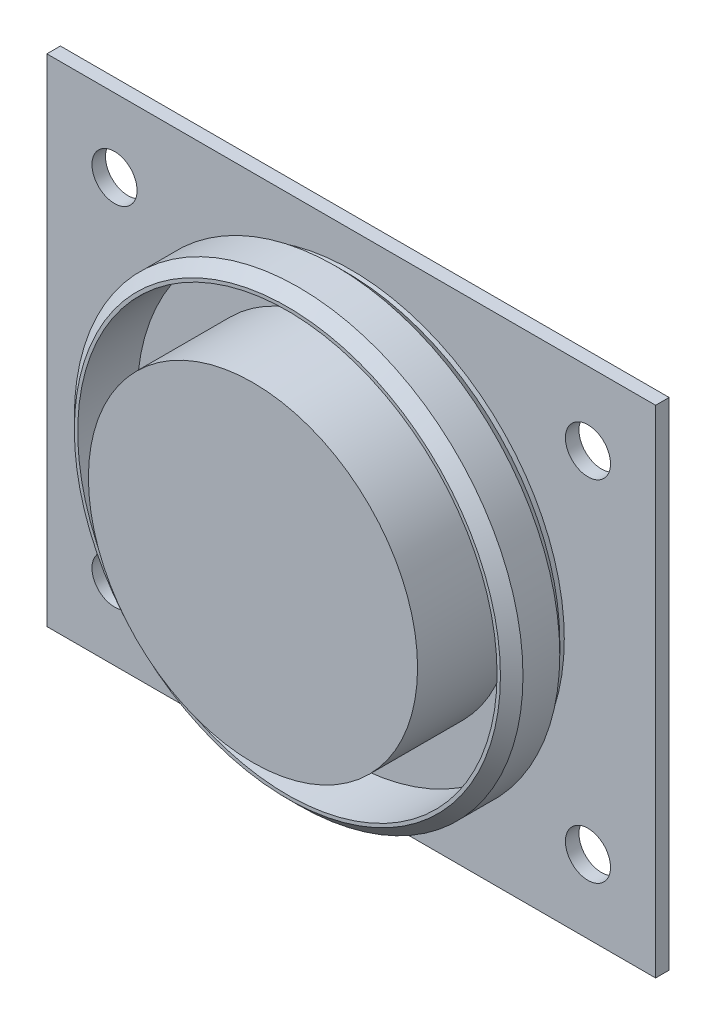
SolidWorks part; units mm, degrees
material "Acciaio inossidabile (ferroso)"
ref_plane "Piano frontale" through (0, 0, 0) normal (0, 0, 1) x (1, 0, 0)
ref_plane "Piano superiore" through (0, 0, 0) normal (0, 1, 0) x (1, 0, 0)
ref_plane "Piano destro" through (0, 0, 0) normal (1, 0, 0) x (0, 0, -1)
other "Centro di massa"
sketch "Schizzo1" plane through (0, 0, 0) normal (0, 0, 1) x (1, 0, 0)
  line L1 (-67.5, 55) -> (67.5, 55)
  line L2 (-67.5, 55) -> (-67.5, -55)
  line L3 (-67.5, -55) -> (67.5, -55)
  line L4 (67.5, 55) -> (67.5, -55)
  line L5 (-67.5, 55) -> (67.5, -55) construction
  line L6 (-67.5, -55) -> (67.5, 55) construction
  line L7 (52.5, -38.75) -> (-52.5, -38.75) construction
  line L8 (52.5, -38.75) -> (52.5, 38.75) construction
  line L9 (52.5, 38.75) -> (-52.5, 38.75) construction
  line L10 (-52.5, -38.75) -> (-52.5, 38.75) construction
  line L11 (52.5, -38.75) -> (-52.5, 38.75) construction
  line L12 (52.5, 38.75) -> (-52.5, -38.75) construction
  circle A0 centre (-52.5, 38.75) radius 5
  circle A1 centre (-52.5, -38.75) radius 5
  circle A2 centre (52.5, -38.75) radius 5
  circle A3 centre (52.5, 38.75) radius 5
  point P0 (0, 0)
  point P6 (0, 0)
  dimension "D5" = 10
  dimension "D1" = 135
  dimension "D2" = 110
  dimension "D3" = 77.5
  dimension "D4" = 15
extrude "Estrusione-Estrusione1" add sketch "Schizzo1" along normal blind 3
sketch "Schizzo3" plane through (0, 0, 0) normal (0, 1, 0) x (1, 0, 0)
  line L0 (0, -4) -> (0, 0) construction
  line L1 (67.5, -3) -> (-67.5, -3) construction
  line L2 (67.5, 0) -> (-67.5, 0) construction
  line L3 (46.5, -4) -> (47.25, -4) construction
  line L4 (47.25, -4) -> (49.75, -6.5)
  line L5 (49.75, -6.5) -> (49.75, -14.66)
  line L6 (49.75, -14.66) -> (47.25, -17.16)
  line L7 (47.25, -17.16) -> (46.5, -17.16)
  line L8 (46.5, -17.16) -> (46.5, -4)
  line L9 (0, -4) -> (0, -3)
  line L10 (0, -4) -> (36.5, -4) construction
  line L11 (0, -4) -> (0, -24.79)
  line L12 (0, -24.79) -> (36.5, -24.79)
  line L13 (36.5, -4) -> (36.5, -24.79)
  line L14 (0, -4) -> (36.5, -24.79) construction
  line L15 (0, -24.79) -> (36.5, -4) construction
  line L16 (36.5, -4) -> (46.5, -4)
  line L17 (47.25, -4) -> (47.25, -3)
  line L18 (0, -3) -> (47.25, -3)
  point P17 (18.25, -14.395)
  dimension "D1" = 135
  dimension "D2" = 135
  dimension "D3" = 13.16
  dimension "D4" = 0.75
  dimension "D5" = 1
  dimension "D6" = 3.25
  dimension "D7" = 10
  dimension "D8" = 46.5
  dimension "D9" = 1
  dimension "D10" = 20.79
revolve "Rivoluzione1" add sketch "Schizzo3" angle 360 about L0
other "Punto di riferimento centro di massa1"
ref_axis "Assi1" through (0, 0, -31.8243) along (0, 0, 1)
ref_plane "Piano1" through (0, 0, 9.8154) normal (0, 0, -1) x (-1, 0, 0)
